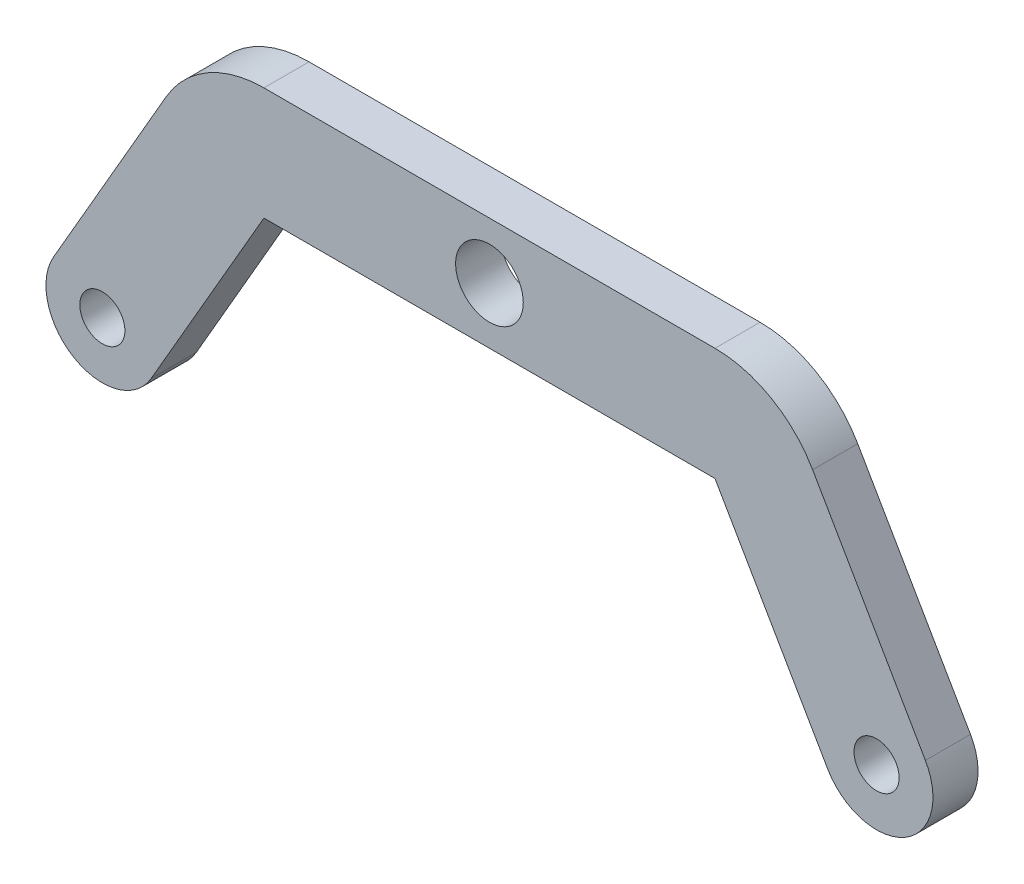
SolidWorks part; units mm, degrees
ref_plane "Front Plane" through (0, 0, 0) normal (0, 0, 1) x (1, 0, 0)
ref_plane "Top Plane" through (0, 0, 0) normal (0, 1, 0) x (1, 0, 0)
ref_plane "Right Plane" through (0, 0, 0) normal (1, 0, 0) x (0, 0, -1)
ref_axis "X" through (-88.99, 0, 0) along (1, 0, 0)
ref_axis "Y" through (0, 55, 0) along (0, -1, 0)
ref_axis "Z" through (0, 0, -88.99) along (0, 0, 1)
sketch "Sketch1" plane through (0, 0, 0) normal (0, 0, 1) x (1, 0, 0)
  line L0 (0, 12.5) -> (0, -12.5) construction
  line L1 (-50, 12.5) -> (50, 12.5)
  line L2 (-50, -12.5) -> (50, -12.5)
  line L3 (71.6506, 0) -> (96.6506, -43.3013)
  line L4 (75, -55.8013) -> (50, -12.5)
  line L5 (-75, -55.8013) -> (-50, -12.5)
  line L6 (-71.6506, 0) -> (-96.6506, -43.3013)
  arc A0 (50, 12.5) -> (71.6506, 0) centre (50, -12.5) cw
  arc A1 (96.6506, -43.3013) -> (75, -55.8013) centre (85.8253, -49.5513) cw
  circle A2 centre (0, 0) radius 7.5
  arc A3 (-96.6506, -43.3013) -> (-75, -55.8013) centre (-85.8253, -49.5513) ccw
  arc A4 (-50, 12.5) -> (-71.6506, 0) centre (-50, -12.5) ccw
  circle A5 centre (-85.8253, -49.5513) radius 5
  circle A6 centre (85.8253, -49.5513) radius 5
  point P4 (0, 0)
  dimension "D1" = 25
  dimension "D5" = 15
  dimension "D6" = 10
  dimension "D2" = 50
  dimension "D3" = 60
  dimension "D4" = 50
extrude "Boss-Extrude1" add sketch "Sketch1" along normal mid plane 10
